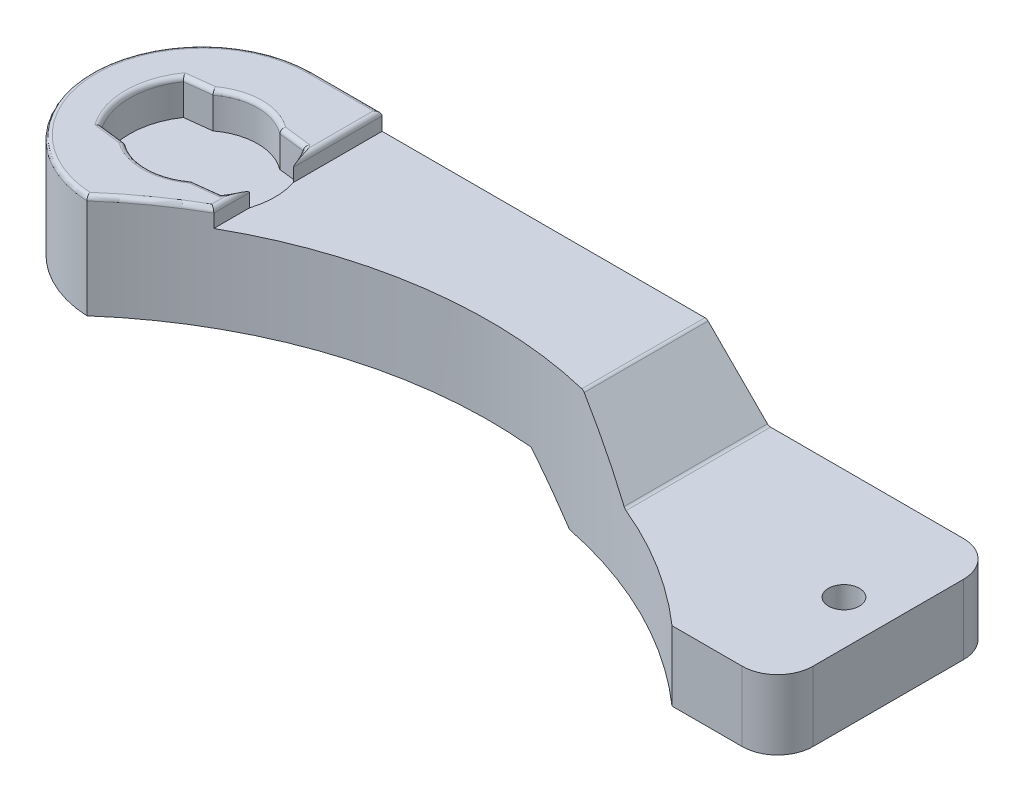
SolidWorks part; units mm, degrees
ref_plane "Front Plane" through (0, 0, 0) normal (0, 0, 1) x (1, 0, 0)
ref_plane "Top Plane" through (0, 0, 0) normal (0, 1, 0) x (1, 0, 0)
ref_plane "Right Plane" through (0, 0, 0) normal (1, 0, 0) x (0, 0, -1)
sketch "Sketch1" plane through (0, 0, 0) normal (0, 1, 0) x (1, 0, 0)
  line L1 (-45, 12.5) -> (45, 12.5)
  line L2 (-45, 12.5) -> (-45, -12.5)
  line L3 (-45, -12.5) -> (45, -12.5)
  line L4 (45, 12.5) -> (45, -12.5)
  dimension "D1" = 90
  dimension "D2" = 45
  dimension "D3" = 25
  dimension "D4" = 12.5
extrude "Boss-Extrude1" add sketch "Sketch1" along normal blind 16.87
sketch "Sketch3" plane through (0, 16.87, 0) normal (0, 1, 0) x (1, 0, 0)
  line L0 (-39.2721, 4.625) -> (-36.2721, 4.9834)
  line L5 (-45, 12.5) -> (-45, -12.5) construction
  line L6 (-45, -12.5) -> (45, -12.5) construction
  line L7 (-39.2721, -4.625) -> (-36.2721, -4.9834)
  line L12 (-32.5, 6.25) -> (-32.5, -6.25) construction
  line L13 (-25.7279, -4.625) -> (-28.7279, -4.9834)
  line L14 (-25.7279, 4.625) -> (-28.7279, 4.9834)
  arc A0 (-28.7279, 4.9834) -> (-36.2721, 4.9834) centre (-32.5, 0) ccw
  arc A3 (-36.2721, -4.9834) -> (-28.7279, -4.9834) centre (-32.5, 0) ccw
  arc A4 (-39.2721, -4.625) -> (-39.2721, 4.625) centre (-32.5, 0) cw
  arc A5 (-25.7279, -4.625) -> (-25.7279, 4.625) centre (-32.5, 0) ccw
  dimension "D2" = 12.5
  dimension "D3" = 3
  dimension "D5" = 8.2007
  dimension "D4" = 3
  dimension "D6" = 12.5
  dimension "D7" = 12.5
  dimension "D10" = 6.7721
  dimension "D13" = 9.25
extrude "Cut-Extrude2" cut sketch "Sketch3" against normal blind 4
sketch "Esquisse2" plane through (0, 0, 12.5) normal (0, 0, 1) x (1, 0, 0)
  line L0 (10, 16.87) -> (19, 7.87)
  line L1 (45, 16.87) -> (10, 16.87)
  line L2 (45, 16.87) -> (45, 7.87)
  line L3 (45, 7.87) -> (10, 7.87)
  line L4 (10, 16.87) -> (10, 7.87)
  line L5 (-45, 0) -> (10, 0)
  line L8 (10, 0) -> (10, 7.87)
  line L9 (10, 0) -> (4.88, 5.12)
  line L10 (4.88, 5.12) -> (-45, 5.12)
  line L11 (-45, 5.12) -> (-45, 0)
  line M3 (-45, 0) -> (45, 0)
  line M4 (45, 0) -> (45, 16.87)
  line M5 (45, 16.87) -> (-45, 16.87)
  line M6 (-45, 16.87) -> (-45, 0)
  dimension "D1" = 35
  dimension "D2" = 9
  dimension "D3" = 45
  dimension "D4" = 45
  dimension "D5" = 2.75
extrude "Enlèv. mat.-Extru.1" cut sketch "Esquisse2" against normal blind 34 contours L8 M3 M6 | L4 L3 M5 M4 region at (29.6393, 12.5913, 12.5) region at (-18.7592, 2.5183, 12.5)
fillet "Fillet1" 2 edges at (-45, 10.995, 12.5) (-45, 10.995, -12.5) type full round first side face at (5.485, 7.465, 12.5) second side face at (5.485, 7.465, -12.5) middle face at (-45, 10.995, 0)
sketch "Esquisse5" plane through (0, 0, 0) normal (0, -1, 0) x (-1, 0, 0)
  line L0 (-45, -12.5) -> (-45, 12.5) construction
  circle A0 centre (-40, 0) radius 1.75
  dimension "D2" = 3.5
  dimension "D1" = 5
extrude "Enlèv. mat.-Extru.4" cut sketch "Esquisse5" against normal through all
fillet "Fillet3" radius 4 2 edges at (45, 3.935, -12.5) (45, 3.935, 12.5)
sketch "Sketch8" plane through (0, 16.87, 0) normal (0, 1, 0) x (1, 0, 0)
  line L1 (-24.6881, 14.1476) -> (13.3414, 14.1476)
  line L2 (-24.6881, 14.1476) -> (-24.6881, -6.796)
  line L3 (-24.6881, -6.796) -> (13.3414, -6.796)
  line L4 (13.3414, 14.1476) -> (13.3414, -6.796)
  dimension "D1" = 38.0295
  dimension "D2" = 20.9436
  dimension "D3" = 14.1476
  dimension "D4" = 24.6881
extrude "Cut-Extrude6" cut sketch "Sketch8" against normal blind 2
sketch "Esquisse17" plane through (0, 5.12, 0) normal (0, -1, 0) x (1, 0, 0)
  circle A0 centre (-32.5, 0) radius 6.45
  dimension "D1" = 12.9
extrude "Enlèv. mat.-Extru.7" cut sketch "Esquisse17" against normal blind 3.6
sketch "Esquisse18" plane through (0, 0, 0) normal (0, 1, 0) x (1, 0, 0)
  circle A0 centre (0, -50) radius 50
  dimension "D2" = 100
  dimension "D1" = 50
extrude "Enlèv. mat.-Extru.8" cut sketch "Esquisse18" against normal through all and the other way through all
fillet "Fillet4" radius 0.5 16 edges at (-28.5941, 16.87, -12.5) (19, 7.87, -4.3747) (12, 14.87, -5.5193) (-37.7721, 16.87, -4.8042) (-32.5, 16.87, -6.25) (-37.7721, 16.87, 4.8042) (-24.6881, 16.87, 4.5077) (-32.5, 16.87, 6.25) (-40.7007, 16.87, 0) (-24.6881, 16.87, -7.4976) (-29.0267, 16.87, 9.2882) (-44.9969, 16.87, -0.279) (-25.1307, 16.87, 3.5979) (-25.1307, 16.87, -3.5979) (-27.2279, 16.87, -4.8042) (-27.2279, 16.87, 4.8042)
